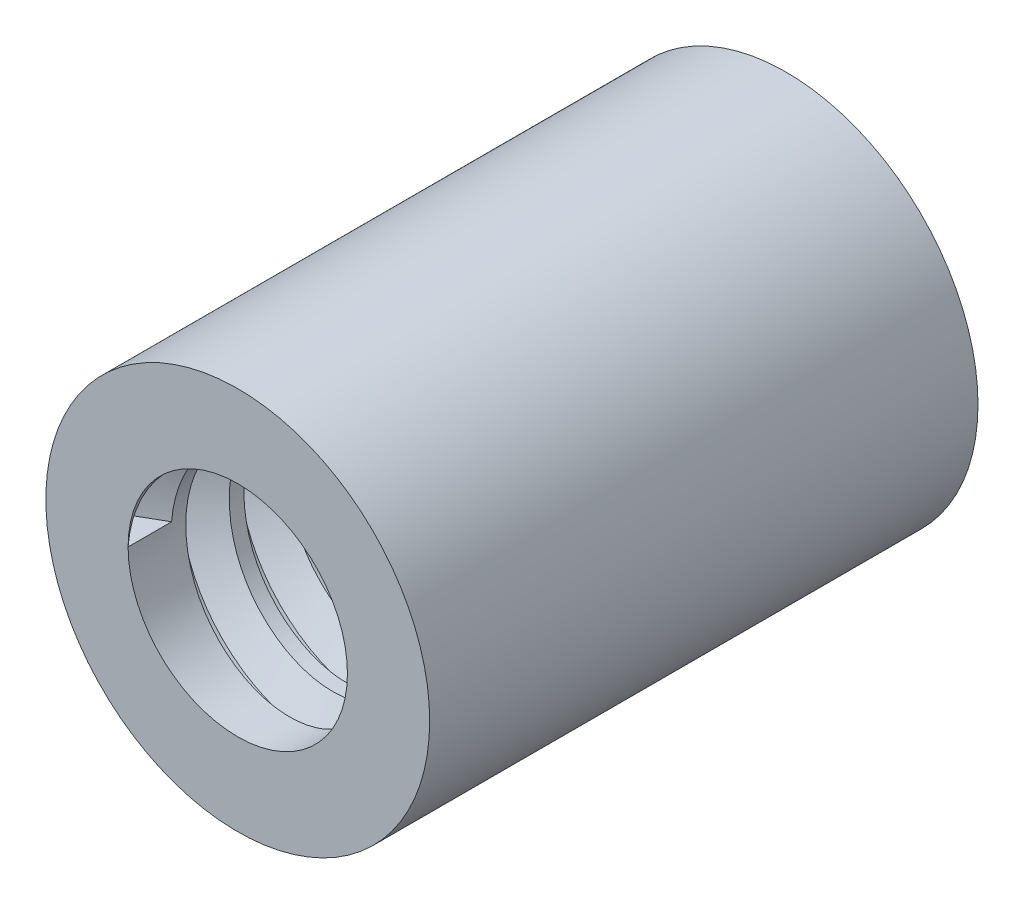
SolidWorks part; units mm, degrees
ref_plane "Front Plane" through (0, 0, 0) normal (0, 0, 1) x (1, 0, 0)
ref_plane "Top Plane" through (0, 0, 0) normal (0, 1, 0) x (1, 0, 0)
ref_plane "Right Plane" through (0, 0, 0) normal (1, 0, 0) x (0, 0, -1)
sketch "Sketch1" plane through (0, 0, 0) normal (0, 0, 1) x (1, 0, 0)
  circle A0 centre (0, 0) radius 3.5
  dimension "D1" = 7
extrude "Boss-Extrude1" add sketch "Sketch1" along normal blind 10
sketch "Sketch2" plane through (0, 0, 10) normal (0, 0, 1) x (1, 0, 0)
  circle A0 centre (0, 0) radius 2
  dimension "D1" = 4
extrude "Cut-Extrude1" cut sketch "Sketch2" against normal blind 7
thread "Thread1" pitch 1.0583 method cut profile "Thread Profile1" start angle 0, offset 0, length 7, pitch 1.0583, diameter 4
ref_plane "Plane1" through (-2, 0, 10) normal (0, -1, 0) x (-1, 0, 0)
sketch "Thread Profile1" plane through (-2, 0, 10) normal (0, -1, 0) x (-1, 0, 0)
  line L0 (0, 0) -> (0, 1.0583) construction
  line L1 (0, 0) -> (0.5728, 0.3307)
  line L2 (0.5728, 0.3307) -> (0.5728, 0.463)
  line L3 (0.5728, 0.463) -> (0, 0.7937)
  line L4 (0.5728, 0.3969) -> (0, 0.3969) construction
  line L11 (0, 0) -> (0, 0.7937)
  point P2 (0, 0)
  dimension "Pitch" = 1.0583
  dimension "Profile_Angle" = 60
  dimension "Profile_Land" = 0.1323
  dimension "Profile_Height" = 0.5728
